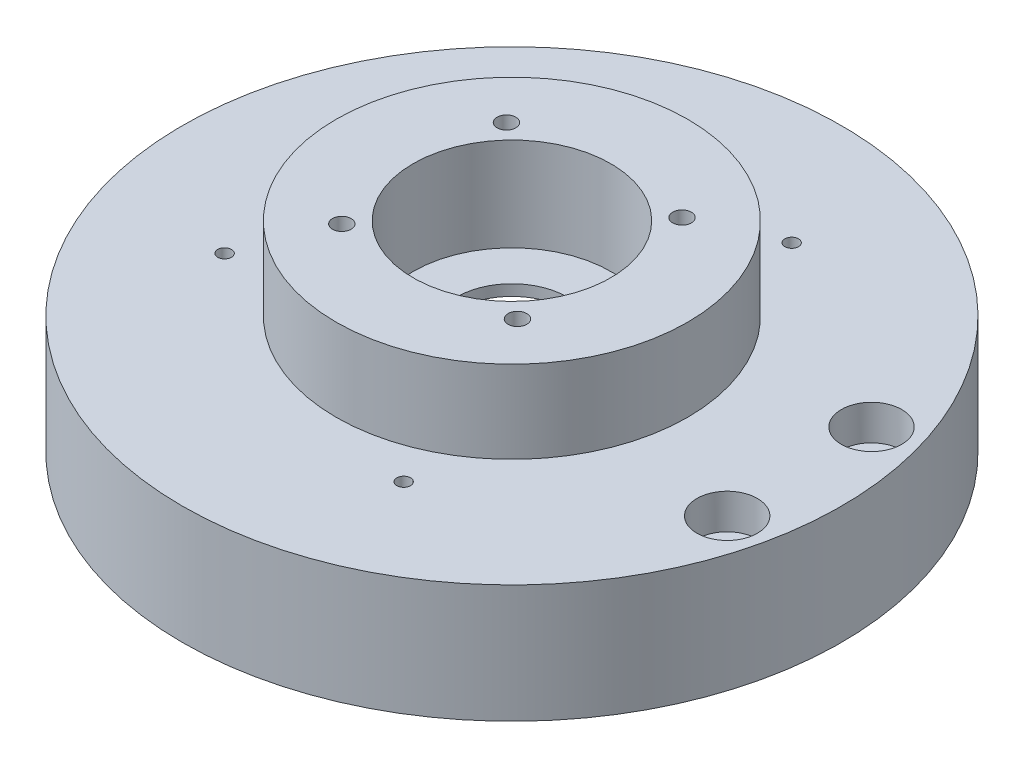
SolidWorks part; units mm, degrees
material "6061 Alloy"
ref_plane "Front Plane" through (0, 0, 0) normal (0, 0, 1) x (1, 0, 0)
ref_plane "Top Plane" through (0, 0, 0) normal (0, 1, 0) x (1, 0, 0)
ref_plane "Right Plane" through (0, 0, 0) normal (1, 0, 0) x (0, 0, -1)
sketch "Sketch1" plane through (0, 0, 0) normal (0, 1, 0) x (1, 0, 0)
  circle A0 centre (0, 0) radius 60
  dimension "D1" = 120
extrude "Boss-Extrude1" add sketch "Sketch1" along normal blind 36.5
sketch "Sketch2" plane through (0, 0, 0) normal (0, -1, 0) x (-1, 0, 0)
  circle A2 centre (0, 0) radius 55
  circle A3 centre (0, 0) radius 50
  circle A4 centre (0, 0) radius 60 construction
  dimension "D1" = 5
  dimension "D2" = 5
extrude "Cut-Extrude1" cut sketch "Sketch2" against normal blind 5 contours A2 A3 region at (53.4444, 0, 0)
sketch "Sketch4" plane through (0, 0, 0) normal (0, 0, 1) x (1, 0, 0)
  line L0 (42, 0) -> (42, 9)
  line L1 (-50, 0) -> (50, 0) construction
  line L2 (42, 9) -> (32.5, 9)
  line L3 (32.5, 9) -> (32.5, 16.5)
  line L5 (0, 30.3215) -> (0, 0)
  line L6 (0, 0) -> (42, 0)
  line L7 (0, 0) -> (0, 32.1539) construction
  line L8 (32.5, 16.5) -> (29, 16.5)
  line L9 (29, 16.5) -> (29, 17.5)
  line L10 (29, 17.5) -> (10, 17.5)
  line L11 (10, 17.5) -> (10, 30.3215)
  line L12 (10, 30.3215) -> (0, 30.3215)
  line L13 (-60, 0) -> (60, 0) construction
  dimension "D1" = 84
  dimension "D2" = 9
  dimension "D3" = 16.5
  dimension "D4" = 29
  dimension "D5" = 20
  dimension "D6" = 65
  dimension "D7" = 17.5
revolve "Cut-Revolve1" cut sketch "Sketch4" angle 360 about L7
sketch "Sketch5" plane through (0, 0, 0) normal (0, 0, 1) x (1, 0, 0)
  line L0 (60, 36.5) -> (-60, 36.5) construction
  line L1 (0, 36.5) -> (18, 36.5)
  line L2 (0, 36.5) -> (0, 19.5)
  line L3 (0, 19.5) -> (18, 19.5)
  line L4 (18, 36.5) -> (18, 19.5)
  line L5 (0, 19.5) -> (0, 62.8395) construction
  dimension "D1" = 36
  dimension "D2" = 17
revolve "Cut-Revolve2" cut sketch "Sketch5" angle 360 about L2
hole_wizard "CBORE for M6 Hex Socket Head Cap Screw1" positions "Sketch6" profile "Sketch7" counterbore size "M6" standard "ISO" end condition through all
sketch "Sketch6" plane through (0, 36.5, 0) normal (0, 1, 0) x (1, 0, 0)
  arc A0 (53.9866, -10.5096) -> (49.0959, -9.4651) centre (51.1242, -11.9402) ccw construction
  arc A1 (48.381, 12.6204) -> (53.1939, 13.979) centre (50.2449, 15.2216) ccw construction
  point P0 (51.1242, -11.9402)
  point P2 (50.2449, 15.2216)
sketch "Sketch7" plane through (51.1242, 36.5, 11.9402) normal (1, 0, 0) x (0, 0, 1)
  line L0 (0, 0) -> (0, 36.5)
  line L1 (0, 36.5) -> (3.2, 36.5)
  line L3 (3.2, 36.5) -> (3.2, 21.4)
  line L4 (3.2, 21.4) -> (5.5, 21.4)
  line L5 (5.5, 21.4) -> (5.5, 0)
  line L7 (5.5, 0) -> (0, 0)
  line L11 (0, -6.35) -> (0, 107.95) construction
  dimension "Thru Hole Dia." = 6.4
  dimension "Thru Hole Depth" = 36.5
  dimension "C'Bore Dia." = 11
  dimension "C'Bore Depth" = 21.4
hole_wizard "M3 Clearance Hole1" positions "Sketch8" profile "Sketch9" hole size "M3" standard "ISO" end condition through all
sketch "Sketch8" plane through (0, 36.5, 0) normal (0, 1, 0) x (1, 0, 0)
  point P0 (14.9846, 15.9872)
  point P3 (15.9872, -14.9846)
  point P6 (-14.9846, -15.9872)
  point P9 (-15.9872, 14.9846)
sketch "Sketch9" plane through (14.9846, 36.5, -15.9872) normal (1, 0, 0) x (0, 0, 1)
  line L0 (0, 0) -> (0, 36.5)
  line L1 (0, 36.5) -> (1.7, 36.5)
  line L2 (1.7, 36.5) -> (1.7, 0)
  line L5 (1.7, 0) -> (0, 0)
  line L11 (0, -6.35) -> (0, 107.95) construction
  dimension "Thru Hole Dia." = 3.4
  dimension "Thru Hole Depth" = 36.5
hole_wizard "CBORE for M3 Hex Socket Head Cap Screw1" positions "Sketch10" profile "Sketch11" counterbore size "M3" standard "ISO" end condition through all
sketch "Sketch10" plane through (0, 17.5, 0) normal (0, -1, 0) x (-1, 0, 0)
  point P0 (15.9872, 14.9846)
  point P3 (-14.9846, 15.9872)
  point P6 (-15.9872, -14.9846)
  point P9 (14.9846, -15.9872)
sketch "Sketch11" plane through (-15.9872, 17.5, -14.9846) normal (1, 0, 0) x (0, 0, -1)
  line L0 (0, 0) -> (0, 19)
  line L1 (0, 19) -> (1.7, 19)
  line L3 (1.7, 19) -> (1.7, 5.4)
  line L4 (1.7, 5.4) -> (3.25, 5.4)
  line L5 (3.25, 5.4) -> (3.25, 0)
  line L7 (3.25, 0) -> (0, 0)
  line L11 (0, -6.35) -> (0, 107.95) construction
  dimension "Thru Hole Dia." = 3.4
  dimension "Thru Hole Depth" = 19
  dimension "C'Bore Dia." = 6.5
  dimension "C'Bore Depth" = 5.4
sketch "Sketch12" plane through (0, 0, 0) normal (0, 0, 1) x (1, 0, 0)
  line L1 (-60, 36.5) -> (-32, 36.5)
  line L2 (-60, 36.5) -> (-60, 21.5)
  line L3 (-60, 21.5) -> (-32, 21.5)
  line L4 (-32, 36.5) -> (-32, 21.5)
  dimension "D1" = 28
  dimension "D2" = 15
revolve "Cut-Revolve3" cut sketch "Sketch12" angle 360 about axis through (0, 36.5, 0) along (0, -1, 0)
hole_wizard "M3 Tapped Hole1" positions "Sketch13" profile "Sketch14" tap size "M3" standard "ISO"
sketch "Sketch13" plane through (0, 21.5, 0) normal (0, 1, 0) x (1, 0, 0)
  point P0 (13.9362, 36.9866)
  point P3 (-36.9866, 13.9362)
  point P6 (-36.0079, -16.2991)
  point P9 (16.2991, -36.0079)
sketch "Sketch14" plane through (13.9362, 21.5, -36.9866) normal (1, 0, 0) x (0, 0, 1)
  line L0 (0, 0) -> (0, 8.2511)
  line L1 (0, 8.2511) -> (1.25, 7.5)
  line L2 (1.25, 7.5) -> (1.25, 0)
  line L5 (1.25, 0) -> (0, 0)
  line L10 (0, 8.2511) -> (-1.25, 7.5) construction
  line L11 (0, -6.35) -> (0, 107.95) construction
  dimension "Tap Drill Dia." = 2.5
  dimension "Tap Drill Depth" = 7.5
  dimension "Drill Angle" = 118
